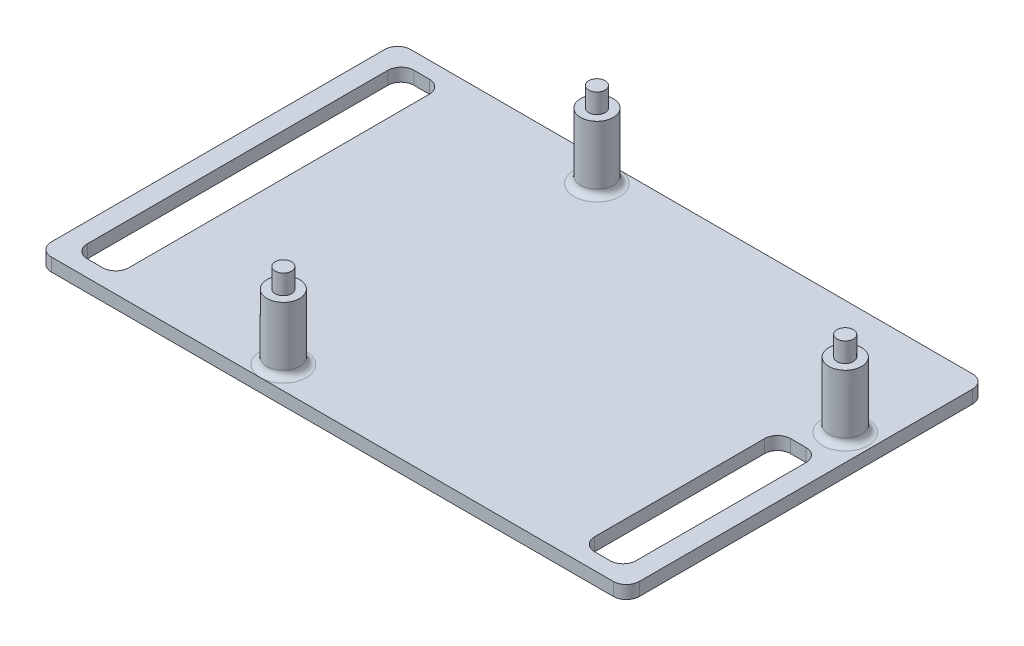
SolidWorks part; units mm, degrees
ref_plane "Front Plane" through (0, 0, 0) normal (0, 0, 1) x (1, 0, 0)
ref_plane "Top Plane" through (0, 0, 0) normal (0, 1, 0) x (1, 0, 0)
ref_plane "Right Plane" through (0, 0, 0) normal (1, 0, 0) x (0, 0, -1)
sketch "Sketch1" plane through (0, 0, 0) normal (0, 1, 0) x (1, 0, 0)
  line L1 (0, 0) -> (90, 0)
  line L2 (0, 0) -> (0, 55)
  line L3 (0, 55) -> (90, 55)
  line L4 (90, 0) -> (90, 55)
  line L5 (80.65, 32.5) -> (87, 32.5)
  line L6 (80.65, 32.5) -> (80.65, 2.5)
  line L7 (80.65, 2.5) -> (87, 2.5)
  line L8 (87, 32.5) -> (87, 2.5)
  line L9 (3, 52.5) -> (9.35, 52.5)
  line L10 (3, 52.5) -> (3, 2.5)
  line L11 (3, 2.5) -> (9.35, 2.5)
  line L12 (9.35, 52.5) -> (9.35, 2.5)
  line L13 (3, 62.5) -> (87, 62.5) construction
  line L14 (3, 62.5) -> (3, -7.5) construction
  line L15 (3, -7.5) -> (87, -7.5) construction
  line L16 (87, 62.5) -> (87, -7.5) construction
  dimension "D1" = 90
  dimension "D2" = 55
  dimension "D3" = 6.35
  dimension "D4" = 50
  dimension "D5" = 2.5
  dimension "D6" = 3
  dimension "D7" = 3
  dimension "D8" = 84
  dimension "D9" = 70
  dimension "D10" = 7.5
  dimension "D11" = 30
extrude "Boss-Extrude1" add sketch "Sketch1" along normal blind 2
sketch "Sketch2" plane through (0, 2, 0) normal (0, 1, 0) x (1, 0, 0)
  line L0 (87, 62.5) -> (87, -7.5) construction
  line L1 (3, 62.5) -> (87, 62.5) construction
  line L2 (3, -7.5) -> (87, -7.5) construction
  circle A0 centre (34, 51.5) radius 2.5
  circle A1 centre (34, 3.5) radius 2.5
  circle A2 centre (86, 37.5) radius 2.5
  dimension "D1" = 5
  dimension "D2" = 53
  dimension "D3" = 25
  dimension "D4" = 11
  dimension "D5" = 11
  dimension "D6" = 1
extrude "Boss-Extrude2" add sketch "Sketch2" along normal blind 10
sketch "Sketch3" plane through (0, 12, 0) normal (0, 1, 0) x (1, 0, 0)
  circle A0 centre (34, 51.5) radius 1.25
  circle A1 centre (34, 3.5) radius 1.25
  circle A2 centre (86, 37.5) radius 1.25
  dimension "D1" = 2.5
extrude "Boss-Extrude3" add sketch "Sketch3" along normal blind 3
fillet "Fillet1" radius 2 12 edges at (9.35, 1, -52.5) (3, 1, -52.5) (3, 1, -2.5) (9.35, 1, -2.5) (80.65, 1, -2.5) (87, 1, -2.5) (87, 1, -32.5) (80.65, 1, -32.5) (90, 1, -55) (90, 1, 0) (0, 1, 0) (0, 1, -55)
fillet "Fillet2" radius 1 3 edges at (86, 2, -40) (34, 2, -6) (34, 2, -54)
